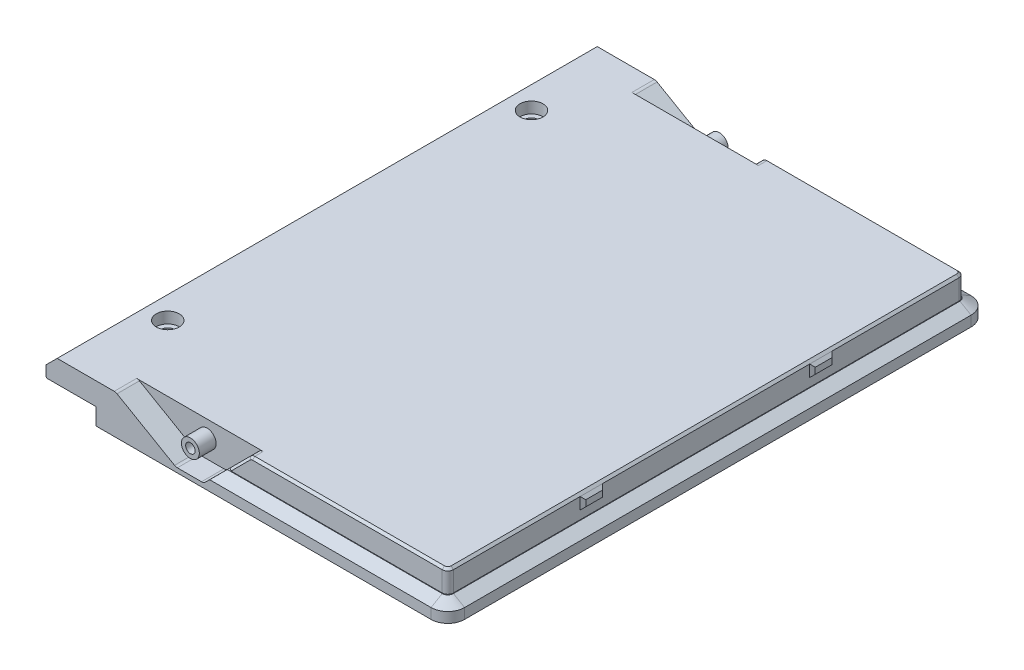
SolidWorks part; units mm, degrees
ref_plane "前视基准面" through (0, 0, 0) normal (0, 0, 1) x (1, 0, 0)
ref_plane "上视基准面" through (0, 0, 0) normal (0, 1, 0) x (1, 0, 0)
ref_plane "右视基准面" through (0, 0, 0) normal (1, 0, 0) x (0, 0, -1)
sketch "草图1" plane through (0, 0, 0) normal (0, 0, 1) x (1, 0, 0)
  line L1 (0, 0) -> (7.1, 0)
  line L3 (0, 4) -> (7.1, 4)
  line L4 (7.1, 0) -> (7.1, 4)
  line L5 (0, 4) -> (-1.8, 4)
  line L6 (0, 0) -> (0, -1.9)
  line L7 (0, -1.9) -> (-1.8, -1.9)
  line L8 (-1.8, 4) -> (-1.8, -1.9)
  dimension "D1" = 1.8
  dimension "D2" = 1.9
  dimension "D3" = 4
  dimension "D4" = 7.1
extrude "凸台-拉伸1" add sketch "草图1" against normal blind 96.5
sketch "草图2" plane through (0, 4, 0) normal (0, 1, 0) x (1, 0, 0)
  line L0 (4.2, 105.0677) -> (4.2, -16.3861) construction
  line L1 (-1.8, 96.5) -> (-1.8, 0) construction
  line L4 (-28.4042, 48.25) -> (44.7588, 48.25) construction
  line L7 (7.1, 0) -> (7.1, 96.5)
  line L8 (7.1, 0) -> (7.1, 96.5)
  line L9 (-1.8, 0) -> (7.1, 0)
  line L11 (7.1, 96.5) -> (-1.8, 96.5)
  line L12 (-1.8, 96.5) -> (-1.8, 0)
  line L13 (-1.8, 0) -> (7.1, 0) construction
  line L15 (7.1, 96.5) -> (-1.8, 96.5) construction
  circle A1 centre (4.2, 80.75) radius 2.05
  circle A3 centre (4.2, 15.75) radius 2.05
  circle A4 centre (4.2, 80.75) radius 1.2
  circle A7 centre (4.2, 15.75) radius 1.2
  dimension "D3" = 65
  dimension "D5" = 4.1
  dimension "D6" = 2.4
  dimension "D1" = 0
  dimension "D2" = 6
extrude "切除-拉伸1" cut sketch "草图2" against normal blind 10 and the other way through all contours A7 | A4
extrude "切除-拉伸2" cut sketch "草图2<3>" against normal blind 2 contours A1 | A3
sketch "草图2<3>" plane through (0, 4, 0) normal (0, 1, 0) x (1, 0, 0) same geometry as "草图2"
chamfer "倒角3" distance 2 angle 45 1 edges at (-1.8, 4, -48.25)
sketch "草图3" plane through (0, -1.9, 0) normal (0, -1, 0) x (1, 0, 0)
  line L0 (0, -96.5) -> (0, 0) construction
  line L1 (-1.8, -96.5) -> (0, -96.5)
  line L2 (-1.8, -96.5) -> (-1.8, -89.1)
  line L3 (-1.8, -89.1) -> (0, -89.1)
  line L4 (0, -96.5) -> (0, -89.1)
  line L5 (-1.8, 0) -> (0, 0)
  line L6 (-1.8, 0) -> (-1.8, -7.4)
  line L7 (-1.8, -7.4) -> (0, -7.4)
  line L8 (0, 0) -> (0, -7.4)
  dimension "D1" = 7.4
extrude "切除-拉伸3" cut sketch "草图3" against normal up to surface (1.9 mm away) up to face at (4.2, 0, -16.95)
chamfer "倒角4" distance 0.2 angle 45 8 edges at (0, -0.95, -89.1) (0, -0.95, -7.4) (0, -1.9, -48.25) (-1.8, 0, -92.8) (-1.8, -0.95, -89.1) (-1.8, 0, -3.7) (-1.8, -0.95, -7.4) (-1.8, -1.9, -48.25)
chamfer "倒角5" distance 0.6 angle 45 2 edges at (-0.9, -1.9, -89.1) (-0.9, -1.9, -7.4)
sketch "草图5" plane through (7.1, 0, 0) normal (1, 0, 0) x (0, 0, -1)
  line L1 (96.5, 4) -> (0, 4)
  line L2 (96.5, 4) -> (96.5, -3)
  line L3 (96.5, -3) -> (0, -3)
  line L4 (0, 4) -> (0, -3)
  line L6 (0, 0) -> (0, 4) construction
  dimension "D1" = 7
extrude "凸台-拉伸3" add sketch "草图5" along normal blind 62.9
sketch "草图6" plane through (0, -3, 0) normal (0, -1, 0) x (1, 0, 0)
  line L0 (61.9, -5.9) -> (17.9, -5.9)
  line L1 (12.8, -11) -> (12.8, -85)
  line L2 (17.9, -90.1) -> (61.9, -90.1)
  line L3 (67, -85) -> (67, -11)
  line L4 (61.9, -6) -> (17.9, -6)
  line L5 (12.9, -11) -> (12.9, -85)
  line L6 (17.9, -90) -> (61.9, -90)
  line L7 (66.9, -85) -> (66.9, -11)
  line L8 (61.9, -6) -> (17.9, -6) construction
  line L9 (12.9, -11) -> (12.9, -85) construction
  line L10 (17.9, -90) -> (61.9, -90) construction
  line L11 (66.9, -85) -> (66.9, -11) construction
  line L12 (12.8, -85) -> (12.8, -88.1)
  line L13 (17.9, -90.1) -> (14.8, -90.1)
  line L14 (61.9, -90.1) -> (65, -90.1)
  line L15 (12.8, -11) -> (12.8, -7.9)
  line L16 (67, -88.1) -> (67, -85)
  line L18 (17.9, -5.9) -> (14.8, -5.9)
  line L21 (61.9, -5.9) -> (65, -5.9)
  line L23 (67, -11) -> (67, -7.9)
  arc A4 (66.9, -11) -> (61.9, -6) centre (61.9, -11) ccw
  arc A5 (17.9, -6) -> (12.9, -11) centre (17.9, -11) ccw
  arc A6 (12.9, -85) -> (17.9, -90) centre (17.9, -85) ccw
  arc A7 (61.9, -90) -> (66.9, -85) centre (61.9, -85) ccw
  arc A8 (66.9, -11) -> (61.9, -6) centre (61.9, -11) ccw construction
  arc A9 (17.9, -6) -> (12.9, -11) centre (17.9, -11) ccw construction
  arc A10 (12.9, -85) -> (17.9, -90) centre (17.9, -85) ccw construction
  arc A11 (61.9, -90) -> (66.9, -85) centre (61.9, -85) ccw construction
  arc A12 (67, -11) -> (61.9, -5.9) centre (61.9, -11) ccw construction
  arc A13 (17.9, -5.9) -> (12.8, -11) centre (17.9, -11) ccw construction
  arc A14 (12.8, -85) -> (17.9, -90.1) centre (17.9, -85) ccw construction
  arc A15 (61.9, -90.1) -> (67, -85) centre (61.9, -85) ccw construction
  arc A16 (12.8, -88.1) -> (14.8, -90.1) centre (14.8, -88.1) ccw
  arc A17 (67, -88.1) -> (65, -90.1) centre (65, -88.1) cw
  arc A18 (65, -5.9) -> (67, -7.9) centre (65, -7.9) cw
  arc A19 (12.8, -7.9) -> (14.8, -5.9) centre (14.8, -7.9) cw
  dimension "D3" = 2
  dimension "D1" = 0
  dimension "D2" = 0.1
extrude "切除-拉伸4" cut sketch "草图6" against normal blind 1
sketch "草图7" plane through (0, 0, -96.5) normal (0, 0, -1) x (-1, 0, 0)
  line L1 (-67.9, 4) -> (-10.6613, 4)
  line L8 (-21.4, -2.2) -> (-26.4, -2.2)
  line L9 (-28.6, 0) -> (-26.4, -2.2)
  line L10 (-67.9, 0) -> (-28.6, 0)
  line L11 (-21.4, -2.2) -> (-10.6613, 4)
  line L12 (-67.9, 4) -> (-67.9, 0)
  line L13 (-28.6, 0) -> (-32.6, 4)
  line L14 (-67.9, 0) -> (-70, 0)
  line L15 (-67.9, 0) -> (-67.9, 4)
  line L16 (-67.9, 4) -> (-70, 4)
  line L17 (-70, 0) -> (-70, 4)
  line L18 (-70, 4) -> (-0.2, 4) construction
  line L19 (-70, -3) -> (-70, 4) construction
  circle A0 centre (-23, 1) radius 1.6
  circle A1 centre (-23, 1) radius 0.85
  line M18 (-0.2, 4) -> (-70, 4)
  line M19 (-70, 4) -> (-70, -3)
  dimension "D8" = 3
  dimension "D9" = 3.2
  dimension "D10" = 1.7
  dimension "D1" = 4
  dimension "D2" = 6.2
  dimension "D3" = 30
  dimension "D4" = 7.2
  dimension "D5" = 135
  dimension "D6" = 41.4
  dimension "D7" = 2.1
  dimension "D11" = 5.6
extrude "切除-拉伸5" cut sketch "草图7" against normal through all contours L14 L12 M18 M19 region at (68.95, 2, -96.5)
extrude "切除-拉伸6" cut sketch "草图7<3>" against normal blind 2.1 contours L10 L13 L1 L12 region at (49.2321, 1.9643, -96.5)
sketch "草图7<3>" plane through (0, 0, -96.5) normal (0, 0, -1) x (-1, 0, 0) same geometry as "草图7"
extrude "切除-拉伸7" cut sketch "草图7<4>" against normal blind 4 contours L13 L9 L8 L11 A0 M18 | A0 A1 | A1 region at (21.6306, 3.772, -96.5) region at (24.5547, 1, -96.5) region at (23, 1, -96.5)
sketch "草图7<4>" plane through (0, 0, -96.5) normal (0, 0, -1) x (-1, 0, 0) same geometry as "草图7"
extrude "切除-拉伸8" cut sketch "草图7<5>" along normal blind 2.1 from surface contours L10 L13 L1 L12 region at (49.2321, 1.9643, -96.5) starting at face at (28.5, 0.42, 0)
sketch "草图7<5>" plane through (0, 0, -96.5) normal (0, 0, -1) x (-1, 0, 0) same geometry as "草图7"
extrude "切除-拉伸9" cut sketch "草图7<6>" along normal blind 4 from surface contours L13 L9 L8 L11 M18 | A0 A1 | A1 region at (21.6306, 3.772, -96.5) region at (24.5547, 1, -96.5) region at (23, 1, -96.5) starting at face at (21.04, 0.42, 0)
sketch "草图7<6>" plane through (0, 0, -96.5) normal (0, 0, -1) x (-1, 0, 0) same geometry as "草图7"
fillet "圆角1" radius 3 2 edges at (70, -1.5, 0) (70, -1.5, -96.5)
fillet "圆角2" radius 1 2 edges at (67.9, 2, -2.1) (67.9, 2, -94.4)
chamfer "倒角6" distance 2 angle 30 5 edges at (47.8, 0, 0) (69.1213, 0, -0.8787) (70, 0, -48.25) (69.1213, 0, -95.6213) (47.8, 0, -96.5) first distance on face at (54.9714, 0, -48.25)
fillet "圆角3" radius 1 8 edges at (32.6, 4, -3.05) (10.6613, 4, -2) (21.4, -2.2, -2) (26.4, -2.2, -2) (10.6613, 4, -94.5) (32.6, 4, -93.45) (26.4, -2.2, -94.5) (21.4, -2.2, -94.5)
extrude "凸台-拉伸4" add sketch "草图7<9>" along normal blind 3 from surface contours A0 starting at face at (22.7653, 0.9, -92.5)
sketch "草图7<9>" plane through (0, 0, -96.5) normal (0, 0, -1) x (-1, 0, 0) same geometry as "草图7"
extrude "切除-拉伸10" cut sketch "草图7<10>" against normal blind 6 contours A1
sketch "草图7<10>" plane through (0, 0, -96.5) normal (0, 0, -1) x (-1, 0, 0) same geometry as "草图7"
extrude "凸台-拉伸5" add sketch "草图7<11>" against normal blind 3 from surface contours A0 A1 | A1 region at (24.5547, 1, -96.5) region at (23, 1, -96.5) starting at face at (22.7653, 0.9, -4)
sketch "草图7<11>" plane through (0, 0, -96.5) normal (0, 0, -1) x (-1, 0, 0) same geometry as "草图7"
extrude "切除-拉伸11" cut sketch "草图7<12>" along normal blind 6 from surface contours A1 region at (23, 1, -96.5) starting at face at (24.6, 1, -1)
sketch "草图7<12>" plane through (0, 0, -96.5) normal (0, 0, -1) x (-1, 0, 0) same geometry as "草图7"
sketch "草图8" plane through (0, -2, 0) normal (0, -1, 0) x (1, 0, 0)
  line L5 (16.8, -86.1) -> (63, -86.1)
  line L6 (16.8, -9.9) -> (16.8, -86.1)
  line L7 (63, -86.1) -> (63, -9.9)
  line L8 (65, -5.9) -> (14.8, -5.9)
  line L9 (12.8, -7.9) -> (12.8, -88.1)
  line L10 (14.8, -90.1) -> (65, -90.1)
  line L11 (67, -88.1) -> (67, -7.9)
  line L12 (65, -5.9) -> (14.8, -5.9) construction
  line L13 (12.8, -7.9) -> (12.8, -88.1) construction
  line L14 (14.8, -90.1) -> (65, -90.1) construction
  line L15 (67, -88.1) -> (67, -7.9) construction
  line L16 (63, -9.9) -> (16.8, -9.9)
  line L18 (16.8, -7.9) -> (16.8, -88.1) construction
  line L19 (14.8, -86.1) -> (65, -86.1) construction
  line L20 (63, -88.1) -> (63, -7.9) construction
  line L21 (65, -9.9) -> (14.8, -9.9) construction
  arc A4 (14.8, -5.9) -> (12.8, -7.9) centre (14.8, -7.9) ccw
  arc A5 (12.8, -88.1) -> (14.8, -90.1) centre (14.8, -88.1) ccw
  arc A6 (65, -90.1) -> (67, -88.1) centre (65, -88.1) ccw
  arc A7 (67, -7.9) -> (65, -5.9) centre (65, -7.9) ccw
  arc A8 (14.8, -5.9) -> (12.8, -7.9) centre (14.8, -7.9) ccw construction
  arc A9 (12.8, -88.1) -> (14.8, -90.1) centre (14.8, -88.1) ccw construction
  arc A10 (65, -90.1) -> (67, -88.1) centre (65, -88.1) ccw construction
  arc A11 (67, -7.9) -> (65, -5.9) centre (65, -7.9) ccw construction
  dimension "D1" = 0
  dimension "D2" = 4
extrude "切除-拉伸12" cut sketch "草图8" against normal offset from surface (5 mm away) 1 up to face at (4.2, 4, -78.7)
chamfer "倒角7" distance 0.4 angle 45 9 edges at (30.4536, 1.8536, -2.1) (32.6315, 3.9239, -2.1) (49.9571, 4, -2.1) (67.6071, 4, -2.3929) (30.4536, 1.8536, -94.4) (67.9, 4, -48.25) (32.6315, 3.9239, -94.4) (67.6071, 4, -94.1071) (49.9571, 4, -94.4)
ref_plane "基准面1" through (7.1, -3, -96.5) normal (0, 0, -1) x (-1, 0, 0)
sketch "草图10" plane through (0, -3, 0) normal (0, -1, 0) x (1, 0, 0)
  line L0 (7.1, 0) -> (7.1, -96.5) construction
  line L1 (7.1, -63.25) -> (16.8, -63.25)
  line L2 (7.1, -63.25) -> (7.1, -33.25)
  line L3 (7.1, -33.25) -> (16.8, -33.25)
  line L4 (16.8, -63.25) -> (16.8, -33.25)
  line L5 (16.8, -9.9) -> (16.8, -86.1) construction
  line L6 (18.8952, -48.25) -> (-14.7957, -48.25) construction
  line L7 (67, -96.5) -> (7.1, -96.5) construction
  line L8 (67, 0) -> (7.1, 0) construction
  dimension "D1" = 30
extrude "切除-拉伸13" cut sketch "草图10" against normal blind 4
chamfer "倒角8" distance 2 angle 45 1 edges at (16.8, 1, -48.25)
sketch "草图12" plane through (0, 3, 0) normal (0, -1, 0) x (1, 0, 0)
  line L0 (12.8, -63.25) -> (12.8, -88.1) construction
  line L1 (22.8, -80.1) -> (12.8, -80.1)
  line L2 (22.8, -80.1) -> (22.8, -90.1)
  line L3 (22.8, -90.1) -> (12.8, -90.1)
  line L4 (12.8, -80.1) -> (12.8, -90.1)
  line L5 (14.8, -90.1) -> (65, -90.1) construction
  dimension "D1" = 10
  dimension "D2" = 10
extrude "凸台-拉伸6" add sketch "草图12" along normal up to surface (5 mm away) up to face at (33.625, -2, -48.0625)
chamfer "倒角9" distance 2 angle 45 3 edges at (9.95, -3, -33.25) (9.95, -3, -63.25) (22.8, 0.5, -80.1)
sketch "草图13" plane through (0, -2, 0) normal (0, -1, 0) x (1, 0, 0)
  circle A0 centre (17.9, -85) radius 2.3
  dimension "D1" = 4.6
extrude "凸台-拉伸7" add sketch "草图13" along normal blind 0.8
sketch "草图14" plane through (0, -3, 0) normal (0, -1, 0) x (1, 0, 0)
  circle A0 centre (56.4, -93.1) radius 0.85
  circle A1 centre (56.4, -3.2) radius 0.85
  dimension "D1" = 1.7
extrude "切除-拉伸14" cut sketch "草图14" against normal blind 3
sketch "草图15" plane through (0, 4, 0) normal (0, 1, 0) x (1, 0, 0)
  line L0 (67.9, 93.4) -> (67.9, 3.1) construction
  line L1 (63.4, 66.75) -> (68.4, 66.75)
  line L2 (63.4, 66.75) -> (63.4, 70.75)
  line L3 (63.4, 70.75) -> (68.4, 70.75)
  line L4 (68.4, 66.75) -> (68.4, 70.75)
  line L5 (63.4, 25.75) -> (68.4, 25.75)
  line L6 (63.4, 25.75) -> (63.4, 29.75)
  line L7 (63.4, 29.75) -> (68.4, 29.75)
  line L8 (68.4, 25.75) -> (68.4, 29.75)
  line L9 (52.6595, 48.25) -> (87.6127, 48.25) construction
  line L10 (33.0142, 94.4) -> (66.9, 94.4) construction
  line L11 (66.9, 2.1) -> (33.0142, 2.1) construction
  dimension "D1" = 4
  dimension "D2" = 5
  dimension "D3" = 0.5
  dimension "D4" = 45
extrude "凸台-拉伸8" add sketch "草图15" against normal blind 1.6 from offset 0.9 offset against normal yes
chamfer "倒角10" distance 0.5 angle 45 6 edges at (68.4, 2.3, -66.75) (68.4, 2.3, -70.75) (68.4, 1.5, -68.75) (68.4, 2.3, -25.75) (68.4, 2.3, -29.75) (68.4, 1.5, -27.75)
chamfer "倒角11" distance 0.5 angle 45 2 edges at (67.9, 3.1, -27.75) (67.9, 3.1, -68.75)
